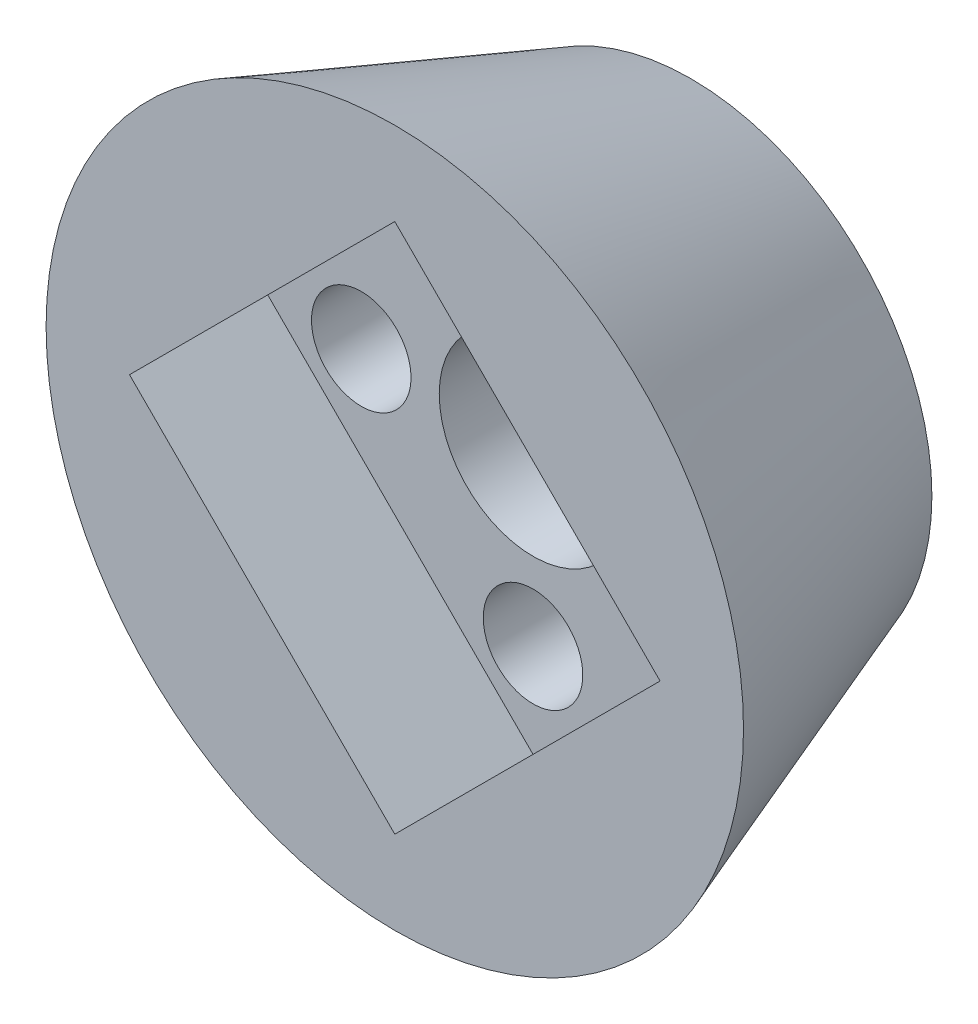
SolidWorks part; units mm, degrees
ref_plane "Front" through (0, 0, 0) normal (0, 0, 1) x (1, 0, 0)
ref_plane "Top" through (0, 0, 0) normal (0, 1, 0) x (1, 0, 0)
ref_plane "Right" through (0, 0, 0) normal (1, 0, 0) x (0, 0, -1)
sketch "GearFaceProfile" plane through (0, 0, 0) normal (0, 0, 1) x (1, 0, 0)
  circle A0 centre (0, 0) radius 12.2
  dimension "D1" = 24.4
extrude "GearFaceExtrude" add sketch "GearFaceProfile" along normal blind 15 draft 20 draft outward yes
sketch "CenterHoleProfile" plane through (0, 0, 0) normal (0, 0, -1) x (-1, 0, 0)
  circle A0 centre (0, 0) radius 4.75
  dimension "D1" = 9.5
extrude "CenterHoleCut" cut sketch "CenterHoleProfile" against normal through all
sketch "ScrewHoleProfile" plane through (0, 0, 0) normal (0, 0, -1) x (-1, 0, 0)
  line L0 (0, 0) -> (0, 8.7) construction
  line L1 (0, 0) -> (8.7, 0) construction
  line L2 (0, 0) -> (0, -8.7) construction
  line L3 (0, 0) -> (-8.7, 0) construction
  circle A2 centre (0, 8.7) radius 2.52
  circle A3 centre (8.7, 0) radius 2.52
  circle A4 centre (0, -8.7) radius 2.52
  circle A5 centre (-8.7, 0) radius 2.52
  dimension "D5" = 5.04
  dimension "D6" = 5.04
  dimension "D7" = 5.04
  dimension "D8" = 5.04
  dimension "D1" = 8.7
  dimension "D2" = 8.7
  dimension "D3" = 8.7
  dimension "D4" = 8.7
extrude "ScrewHoleCut" cut sketch "ScrewHoleProfile" against normal through all
sketch "ShaftCollarAttachmentProfile" plane through (0, 0, 15) normal (0, 0, 1) x (1, 0, 0)
  line L0 (0, 0) -> (0, 13.435) construction
  line L1 (0, 0) -> (13.435, 0) construction
  line L2 (0, 13.435) -> (13.435, 0)
  line L3 (13.435, 0) -> (0, -13.435)
  line L4 (0, -13.435) -> (-13.435, 0)
  line L5 (-13.435, 0) -> (0, 13.435)
  dimension "D1" = 19
  dimension "D2" = 19
extrude "ShaftCollarDockingCut" cut sketch "ShaftCollarAttachmentProfile" against normal blind 7
equation "\"TGMScrewHole-Center\"=8.70mm"
equation "\"TGMScrewHoleDiameter\"=5.04mm"
equation "\"TGMCenterHoleDiameter\"=9.50mm"
equation "\"TGMGearFaceDiameter\"=24.40mm"
equation "\"D1@GearFaceProfile\" = \"TGMGearFaceDiameter\""
equation "\"D1@CenterHoleProfile\" = \"TGMCenterHoleDiameter\""
equation "\"D4@ScrewHoleProfile\" = \"TGMScrewHole-Center\""
equation "\"D1@ScrewHoleProfile\" = \"TGMScrewHole-Center\""
equation "\"D2@ScrewHoleProfile\" = \"TGMScrewHole-Center\""
equation "\"D3@ScrewHoleProfile\" = \"TGMScrewHole-Center\""
equation "\"D5@ScrewHoleProfile\" = \"TGMScrewHoleDiameter\""
equation "\"D6@ScrewHoleProfile\" = \"TGMScrewHoleDiameter\""
equation "\"D8@ScrewHoleProfile\" = \"TGMScrewHoleDiameter\""
equation "\"D7@ScrewHoleProfile\" = \"TGMScrewHoleDiameter\""
equation "\"TGMCylinderLength\"=15.00mm"
equation "\"TGMShaftCollarSideLength\"=19.00mm"
equation "\"D1@ShaftCollarAttachmentProfile\" = \"TGMShaftCollarSideLength\""
equation "\"D2@ShaftCollarAttachmentProfile\" = \"TGMShaftCollarSideLength\""
equation "\"TGMShaftCollarDockingDepth\"=7.00mm"
equation "\"CageLeftBottomEdge\"=22.11mm"
equation "\"CageLeftTopEdge\"=22.11mm"
equation "\"CageRightBottomEdge\"=21.63mm"
equation "\"CageRightTopEdge\"=21.63mm"
equation "\"CageHeight\"=86.04mm"
equation "\"CageLength\"=73.76mm"
equation "\"CageTopScrewClearance\"=10mm"
equation "\"CageBottomScrewClearance\"=25mm"
equation "\"CageLeftTopDepth\"= 11.65mm"
equation "\"CageLeftBottomDepth\"=11.11mm"
equation "\"CageLeftTopHeight\"=8.56175mm"
equation "\"CageLeftBottomHeight\"=16mm"
equation "\"CageRightTopDepth\"= 11.05mm"
equation "\"CageRightBottomDepth\"=10.58mm"
equation "\"CageRightTopHeight\"=9.6mm"
equation "\"CageRightBottomHeight\"=15.49mm"
equation "\"CageLeftTopChannelDepth\"=2.41908mm"
equation "\"CageLeftBottomChannelDepth\"=2.588mm"
equation "\"CageLeftChannelHeight\"=11.7mm"
equation "\"CageRightTopChannelDepth\"=2.32mm"
equation "\"CageRightBottomChannelDepth\"=2.318mm"
equation "\"CageRightChannelHeight\"=10mm"
equation "\"CageChanRelHeight\"=23.99mm"
equation "\"CageChanRelDepth\"=5.492mm"
equation "\"CageChamberRadius\"=16.261mm"
equation "\"CageScrewDiameter\"=4.8mm"
equation "\"CageSetScrewDiameter\"=3.5mm"
equation "\"CageAxleRadius\"=6.639mm"
equation "\"CageAxleKeyHeight\"=1.619mm"
equation "\"CageAxleKeyWidth\"=2.662mm"
equation "\"CageHoseWindowWidth\"=16.29mm"
equation "\"CageHoseWindowHeight\"=26.5mm"
equation "\"CageHoseWindow-Edge\"=8.89mm"
equation "\"CageScrew-VerticalEdge\"=5.0mm"
equation "\"CageScrew-HorizontalEdge\"=7.5mm"
equation "\"CageScrew-HoseCornerScrewEdge\"=4.45mm"
equation "\"CageAxle-BottomEdge\"=56.05mm"
equation "\"CageAxle-FrontEdge\"=46.03mm"
equation "\"CageBackSetScrew-Axle\"=40mm"
equation "\"CageFrontSetScrew-Axle\"=22mm"
equation "\"CageVelocityWindow-BackEdge\"=34.8mm"
equation "\"CageVelocityWindow-BottomEdge\"=27.55mm"
equation "\"CageVelocityWindowHeight\"=22.29mm"
equation "\"CageVelocityWindowWidth\"=12.61mm"
equation "\"TriggerSlot-BottomEdge\"=6.35mm"
equation "\"TriggerSlot-FrontEdge\"=15mm"
equation "\"TriggerSlotSize\"=6.7mm"
equation "\"TriggerRackOffset\"=.236224in"
equation "\"TriggerSlotSizeInt\"=.25in"
equation "\"MotorMountLegLength\"=.25in"
equation "\"GearOffset\"=.264907in"
equation "\"TriggerSlotSpacing\"=.25in"
equation "\"TriggerMiniSlotWidth\"=3.5mm"
equation "\"TriggerRackWidth\"=6.5mm"
equation "\"whitemotordepth\"=11.27mm"
equation "\"whitemotorbackdepth\"=3.845mm"
equation "\"whitemotoraxledepth\" = 3.5mm"
equation "\"whitemotoraxleoffset\"=11.4mm"
equation "\"whitemotorwidth\"=12.07mm"
equation "\"whitemotorheight\"=16.68mm"
equation "\"whitemotorcylinderlength\" =13.04mm"
equation "\"whitemotorcylinderradius\"=3.845mm"
equation "\"whitemotorcylinderoffset\"=2.35mm"
equation "\"whitemotorcutoutlength\"=1.88mm"
equation "\"whitemotorouterrad\"=5mm"
equation "\"whitemotorinnerrad\"=2.95mm"
equation "\"elasticracklength\"=2in"
equation "\"elasticrackpegsize\"=.25in"
equation "\"elasticrackpegbuffer\"=.125in"
equation "\"elasticrackpegspacing\"=1.76476378in"
equation "\"elasticbaybuffer\"=.25in"
equation "\"elasticdepth\"=.125in"
equation "\"elasticbaydepth\"=.75in"
equation "\"motormountwidth\"=12mm"
equation "\"motormountcornerfillet\"=3mm"
equation "\"pandiscradius\"=14in"
equation "\"towermaterialwidth\"=.25in"
equation "\"towerslotlength\"=.5in"
equation "\"towermarkerspace\"=5in"
equation "\"towerslothorizoffset\"=1in"
equation "\"towerslothorizspacing\"=2in"
equation "\"towerslotvertoffset\"=3in"
equation "\"towerslotvertspacing\"=2in"
equation "\"towerheight\"=12in"
equation "\"towerupslot\"=1in"
equation "\"toweraxle\"=.5in"
equation "\"towerplatslotoffset\"=1.5in"
equation "\"towermotorpanelheight\"=10in"
equation "\"towerplatdepth\"=2in"
equation "\"stepperouterrad\"=10mm"
equation "\"stepperscrewsize\"=3.45mm"
equation "\"stepperscrewc2c\"=49.5mm"
equation "\"stepperdepthoffset\"=24mm"
equation "\"stepperhorizoffset\"=22.91mm"
equation "\"shaftslotOD\"=18.8mm"
equation "\"shaftslotID\"=13.28mm"
equation "\"shaftkeywidth\"=2.67mm"
equation "\"shaftkeydepth\"=1.8mm"
equation "\"shaftcollartotaldepth\"=12.5mm"
equation "\"shaftsquaredepth\"=6mm"
equation "\"shaftsetscrewsize\"=3.5mm"
equation "\"shaftkeytightdepth\"=1.85mm"
equation "\"shaftslottightID\"=12.78mm"
equation "\"shaftsetscrewoffset\"=9mm"
equation "\"cagecollartotaldepth\"=10mm"
equation "\"cagecollartotalwidth\"=35mm"
equation "\"cagecollarbasedepth\"=4mm"
